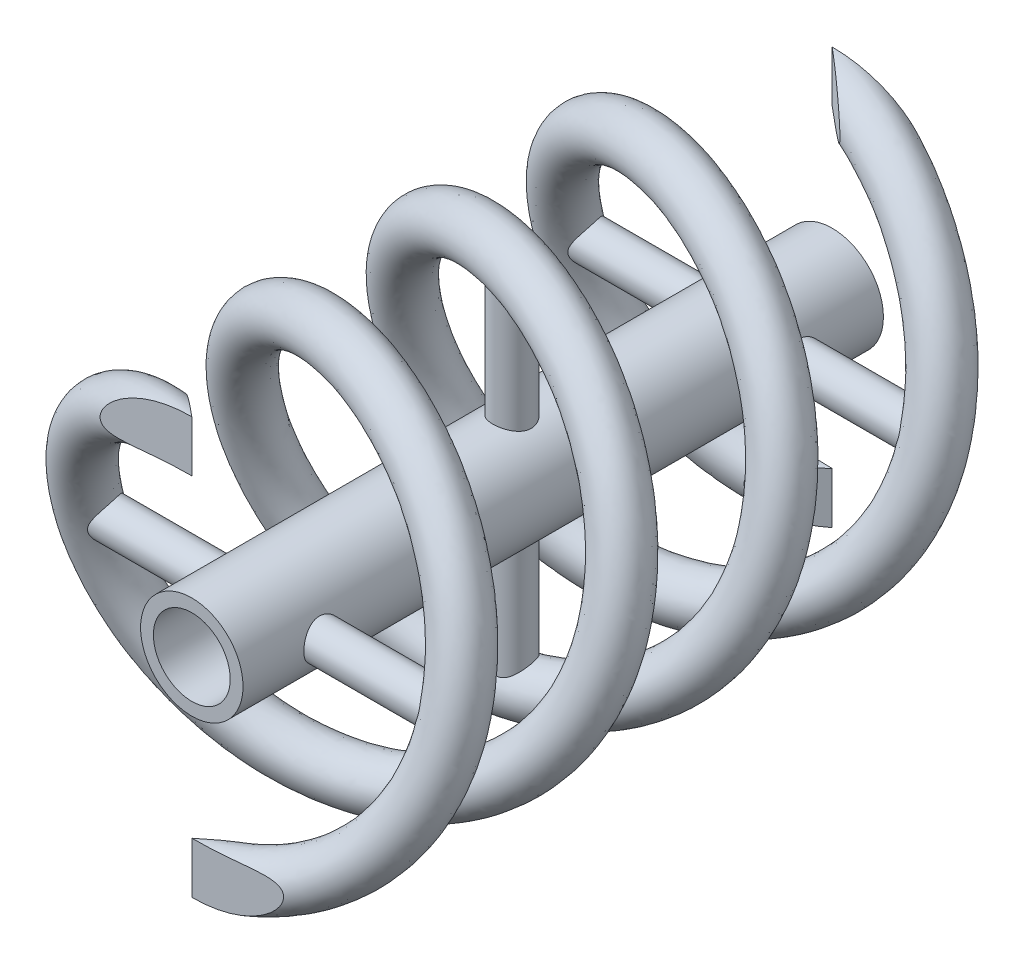
SolidWorks part; units mm, degrees
ref_plane "Front Plane" through (0, 0, 0) normal (0, 0, 1) x (1, 0, 0)
ref_plane "Top Plane" through (0, 0, 0) normal (0, 1, 0) x (1, 0, 0)
ref_plane "Right Plane" through (0, 0, 0) normal (1, 0, 0) x (0, 0, -1)
other "Configuration Table"
sketch "Sketch1" plane through (0, 0, 0) normal (0, 0, 1) x (1, 0, 0)
  circle A0 centre (0, 0) radius 2.85
curve "Helix/Spiral1" pitch 5 height 10 turns 2
sweep "Sweep1" add path "Helix/Spiral1" circular profile diameter 0.8 parameters "D3"=0.8
move or copy body "Body-Move/Copy1" bodies to move or copy 102 copy yes number of copies 1 rotation origin (0, 0, 0) rotation axis (0, 0, 1) rotation angle 180
sketch "Sketch13" plane through (0, 0, 0) normal (0, 0, 1) x (1, 0, 0)
  circle A0 centre (0, 0) radius 0.8
extrude "Boss-Extrude3" add sketch "Sketch13" along normal blind 10
sketch "Sketch26" plane through (0, 0, 0) normal (1, 0, 0) x (0, 0, -1)
  circle A0 centre (-8.75, 0) radius 0.3
  circle A1 centre (-1.25, 0) radius 0.3
  spline S0 degree 3 poles (0, 2.85) (-0.1035, 2.85) (-0.3128, 2.7016) (-0.6249, 2.0677) (-0.9375, 1.119) (-1.25, 0) (-1.5625, -1.119) (-1.875, -2.0677) (-2.1875, -2.7016) (-2.5, -2.9242) (-2.8125, -2.7016) (-3.125, -2.0677) (-3.5417, -0.8028) (-3.9583, 0.8028) (-4.375, 2.0677) (-4.6875, 2.7016) (-5, 2.9242) (-5.3125, 2.7016) (-5.625, 2.0677) (-6.0417, 0.8028) (-6.4583, -0.8028) (-6.875, -2.0677) (-7.1875, -2.7016) (-7.5, -2.9242) (-7.8125, -2.7016) (-8.125, -2.0677) (-8.4375, -1.119) (-8.75, 0) (-9.0625, 1.119) (-9.3751, 2.0677) (-9.6872, 2.7016) (-9.8965, 2.85) (-10, 2.85) knots 0 0 0 0 0.03125 0.0625 0.09375 0.125 0.15625 0.1875 0.21875 0.25 0.28125 0.3125 0.34375 0.40625 0.4375 0.46875 0.5 0.53125 0.5625 0.59375 0.65625 0.6875 0.71875 0.75 0.78125 0.8125 0.84375 0.875 0.90625 0.9375 0.96875 1 1 1 1 construction
extrude "Boss-Extrude5" add sketch "Sketch26" along normal mid plane 6
sketch "Sketch31" plane through (0, 0, 0) normal (0, 1, 0) x (1, 0, 0)
  circle A0 centre (0, -5) radius 0.3
  spline S0 degree 3 poles (0, 0) (0.3708, -0.1035) (1.12, -0.3128) (2.0674, -0.6249) (2.7017, -0.9375) (2.9242, -1.25) (2.7016, -1.5625) (2.0677, -1.875) (0.8028, -2.2917) (-0.8028, -2.7083) (-2.0677, -3.125) (-2.7016, -3.4375) (-2.9242, -3.75) (-2.7016, -4.0625) (-2.0677, -4.375) (-0.8028, -4.7917) (0.8028, -5.2083) (2.0677, -5.625) (2.7016, -5.9375) (2.9242, -6.25) (2.7016, -6.5625) (2.0677, -6.875) (0.8028, -7.2917) (-0.8028, -7.7083) (-2.0677, -8.125) (-2.7016, -8.4375) (-2.9242, -8.75) (-2.7017, -9.0625) (-2.0674, -9.3751) (-1.12, -9.6872) (-0.3708, -9.8965) (0, -10) knots 0 0 0 0 0.03125 0.0625 0.09375 0.125 0.15625 0.1875 0.21875 0.28125 0.3125 0.34375 0.375 0.40625 0.4375 0.46875 0.53125 0.5625 0.59375 0.625 0.65625 0.6875 0.71875 0.78125 0.8125 0.84375 0.875 0.90625 0.9375 0.96875 1 1 1 1 construction
extrude "Boss-Extrude6" add sketch "Sketch31" along normal mid plane 6
sketch "Sketch14" plane through (0, 0, 0) normal (1, 0, 0) x (0, 0, -1)
  line L0 (-10, 0) -> (-10, 4.2029)
  line L1 (-10, 0.8) -> (-10, -0.8) construction
  line L2 (-10, 4.2029) -> (-11.2562, 4.2029)
  line L3 (-11.2562, 4.2029) -> (-11.2562, -3.5466)
  line L4 (-11.2562, -3.5466) -> (-10, -3.5466)
  line L5 (-10, -3.5466) -> (-10, 0)
extrude "Cut-Extrude1" cut sketch "Sketch14" against normal through all both and the other way through all
sketch "Sketch15" plane through (0, 0, 0) normal (1, 0, 0) x (0, 0, -1)
  line L0 (0, 0) -> (0, 4.5649)
  line L1 (0, 4.5649) -> (2.0707, 4.5649)
  line L2 (2.0707, 4.5649) -> (2.0707, -3.8182)
  line L3 (2.0707, -3.8182) -> (0, -3.8182)
  line L4 (0, -3.8182) -> (0, 0)
extrude "Cut-Extrude2" cut sketch "Sketch15" against normal through all both and the other way through all
ref_plane "Plane1" through (0, 3.25, 0) normal (0, 1, 0) x (1, 0, 0)
sketch "Sketch17" plane through (0, 3.25, 0) normal (0, 1, 0) x (1, 0, 0)
  line L0 (0, -10) -> (0.5721, -10)
  line L1 (-0.8, -10) -> (0.8, -10) construction
  line L2 (0.5721, -8.8044) -> (0.5721, -10)
  line L3 (0, -10) -> (-1.4248, -8.8044)
  line L4 (-1.4248, -8.8044) -> (0.5721, -8.8044)
  line L5 (0, 0) -> (-0.5721, 0)
  line L6 (0.8, 0) -> (-0.8, 0) construction
  line L7 (-0.5721, 0) -> (-0.5721, -1.1956)
  line L8 (-0.5721, -1.1956) -> (1.4248, -1.1956)
  line L9 (1.4248, -1.1956) -> (0, 0)
  dimension "D1" = 40
  dimension "D2" = 1.86
  dimension "D3" = 40
  dimension "D4" = 1.86
extrude "Cut-Extrude8" cut sketch "Sketch17" against normal blind 2 and the other way through all
ref_plane "Plane2" through (0, -3.25, 0) normal (0, 1, 0) x (1, 0, 0)
sketch "Sketch19" plane through (0, -3.25, 0) normal (0, 1, 0) x (1, 0, 0)
  line L0 (0, 0) -> (0.5164, 0)
  line L1 (0.8, 0) -> (-0.8, 0) construction
  line L2 (0.5164, 0) -> (0.5164, -1.1956)
  line L3 (0, 0) -> (-1.4248, -1.1956)
  line L4 (-1.4248, -1.1956) -> (0.5164, -1.1956)
  line L5 (0, -10) -> (-0.358, -10)
  line L6 (-0.8, -10) -> (0.8, -10) construction
  line L7 (-0.358, -10) -> (-0.373, -10.0067)
  line L8 (-0.373, -10.0067) -> (-0.373, -8.8044)
  line L9 (-0.373, -8.8044) -> (1.4248, -8.8044)
  line L10 (1.4248, -8.8044) -> (0, -10)
  dimension "D1" = 40
  dimension "D2" = 1.86
  dimension "D3" = 40
  dimension "D4" = 1.86
extrude "Cut-Extrude10" cut sketch "Sketch19" along normal blind 2
sketch "Sketch21" plane through (0, 0, 0) normal (0, 0, 1) x (1, 0, 0)
  circle A0 centre (0, 0) radius 0.6
extrude "Cut-Extrude7" cut sketch "Sketch21" against normal through all both and the other way through all
